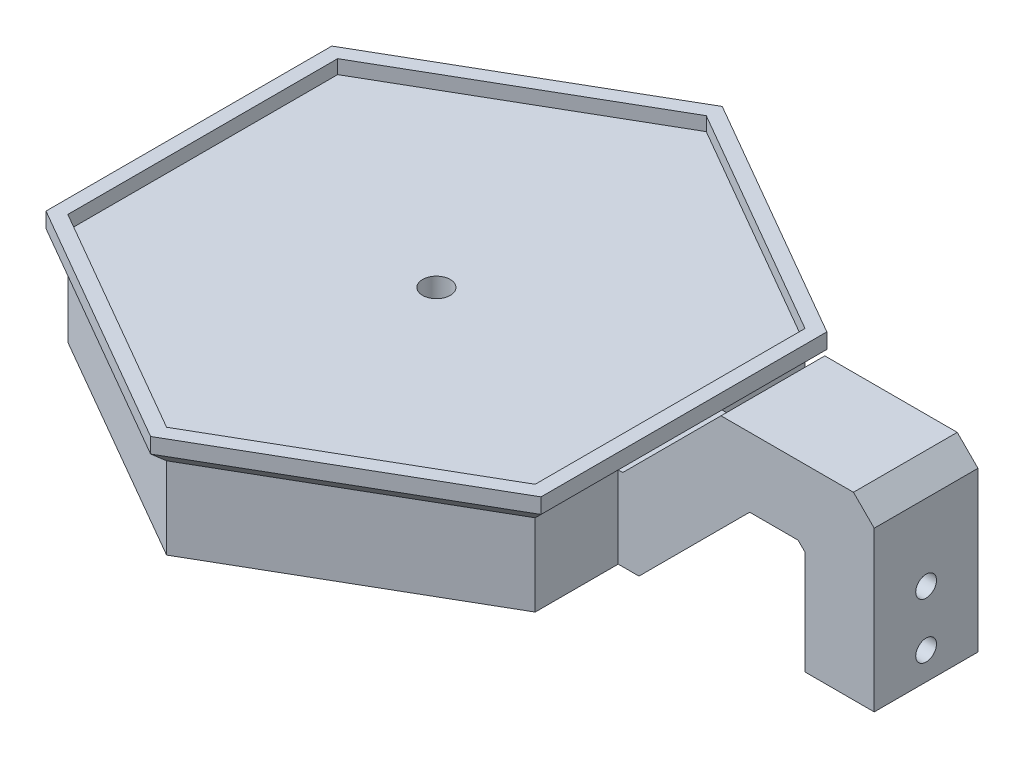
SolidWorks part; units mm, degrees
ref_plane "Front" through (0, 0, 0) normal (0, 0, 1) x (1, 0, 0)
ref_plane "Top" through (0, 0, 0) normal (0, 1, 0) x (1, 0, 0)
ref_plane "Right" through (0, 0, 0) normal (1, 0, 0) x (0, 0, -1)
sketch "Sketch1" plane through (0, 0, 0) normal (0, 1, 0) x (1, 0, 0)
  line L1 (33.775, 19.5) -> (0, 39)
  line L2 (0, 39) -> (-33.775, 19.5)
  line L3 (-33.775, 19.5) -> (-33.775, -19.5)
  line L4 (-33.775, -19.5) -> (0, -39)
  line L5 (0, -39) -> (33.775, -19.5)
  line L6 (33.775, -19.5) -> (33.775, 19.5)
  circle A0 centre (0, 0) radius 33.775 construction
  dimension "D1" = 78
extrude "Boss-Extrude1" add sketch "Sketch1" along normal blind 14
sketch "Sketch2" plane through (0, 14, 0) normal (0, 1, 0) x (1, 0, 0)
  line L0 (0, 41.3094) -> (-35.775, 20.6547)
  line L1 (-35.775, 20.6547) -> (-35.775, -20.6547)
  line L2 (-35.775, -20.6547) -> (0, -41.3094)
  line L3 (0, -41.3094) -> (35.775, -20.6547)
  line L4 (35.775, -20.6547) -> (35.775, 20.6547)
  line L5 (35.775, 20.6547) -> (0, 41.3094)
  line L6 (33.775, -19.5) -> (33.775, 19.5)
  line L7 (33.775, 19.5) -> (0, 39)
  line L8 (0, 39) -> (-33.775, 19.5)
  line L9 (-33.775, 19.5) -> (-33.775, -19.5)
  line L10 (-33.775, -19.5) -> (0, -39)
  line L11 (0, -39) -> (33.775, -19.5)
  line L12 (33.775, -19.5) -> (33.775, 19.5)
  line L13 (33.775, 19.5) -> (0, 39)
  line L14 (0, 39) -> (-33.775, 19.5)
  line L15 (-33.775, 19.5) -> (-33.775, -19.5)
  line L16 (-33.775, -19.5) -> (0, -39)
  line L17 (0, -39) -> (33.775, -19.5)
  dimension "D1" = 0
  dimension "D2" = 2
extrude "Boss-Extrude2" add sketch "Sketch2" along normal blind 2 and the other way blind 0.2
chamfer "Chamfer1" distance 2 angle 45 6 edges at (-33.775, 13.8, 0) (-16.8875, 13.8, -29.25) (16.8875, 13.8, -29.25) (33.775, 13.8, 0) (16.8875, 13.8, 29.25) (-16.8875, 13.8, 29.25)
sketch "Sketch3" plane through (0, 14, 0) normal (0, 1, 0) x (1, 0, 0)
  circle A0 centre (0, 0) radius 2
  dimension "D1" = 4
extrude "Cut-Extrude1" cut sketch "Sketch3" against normal through all
sketch "Sketch5" plane through (0, 0, 0) normal (0, 0, 1) x (1, 0, 0)
  line L0 (33.775, 11.8) -> (34.4329, 11.8)
  line L1 (33.775, 11.8) -> (33.775, 0) construction
  line L2 (34.4329, 11.8) -> (48.6329, 26)
  line L3 (33.775, 0) -> (36.775, 0)
  line L4 (48.6329, 26) -> (70.775, 26)
  line L5 (60.775, 0) -> (60.775, 16)
  line L6 (70.775, 26) -> (70.775, 0)
  line L7 (70.775, 0) -> (60.775, 0)
  line L8 (33.775, 11.8) -> (0, 11.8) construction
  line L9 (60.775, 16) -> (52.775, 16)
  line L10 (52.775, 16) -> (36.775, 0)
  line L11 (33.775, 11.8) -> (35.775, 13.8) construction
  line L12 (33.775, 0) -> (33.775, 11.8)
  dimension "D1" = 10
  dimension "D2" = 10
  dimension "D3" = 16
  dimension "D4" = 26
  dimension "D5" = 135
  dimension "D7" = 8
  dimension "D8" = 3
extrude "Boss-Extrude3" add sketch "Sketch5" along normal mid plane 15
sketch "Sketch6" plane through (60.775, 0, 0) normal (-1, 0, 0) x (0, 0, 1)
  line L0 (-7.5, 0) -> (7.5, 16) construction
  circle A0 centre (0, 12) radius 1.5
  circle A1 centre (0, 4) radius 1.5
  point P4 (0, 8)
  dimension "D1" = 3
  dimension "D2" = 3
  dimension "D3" = 4
  dimension "D4" = 4
extrude "Cut-Extrude2" cut sketch "Sketch6" against normal up to next
chamfer "Chamfer2" distance 1 angle 45 1 edges at (60.775, 16, 0)
chamfer "Chamfer3" distance 3 angle 45 1 edges at (70.775, 26, 0)
